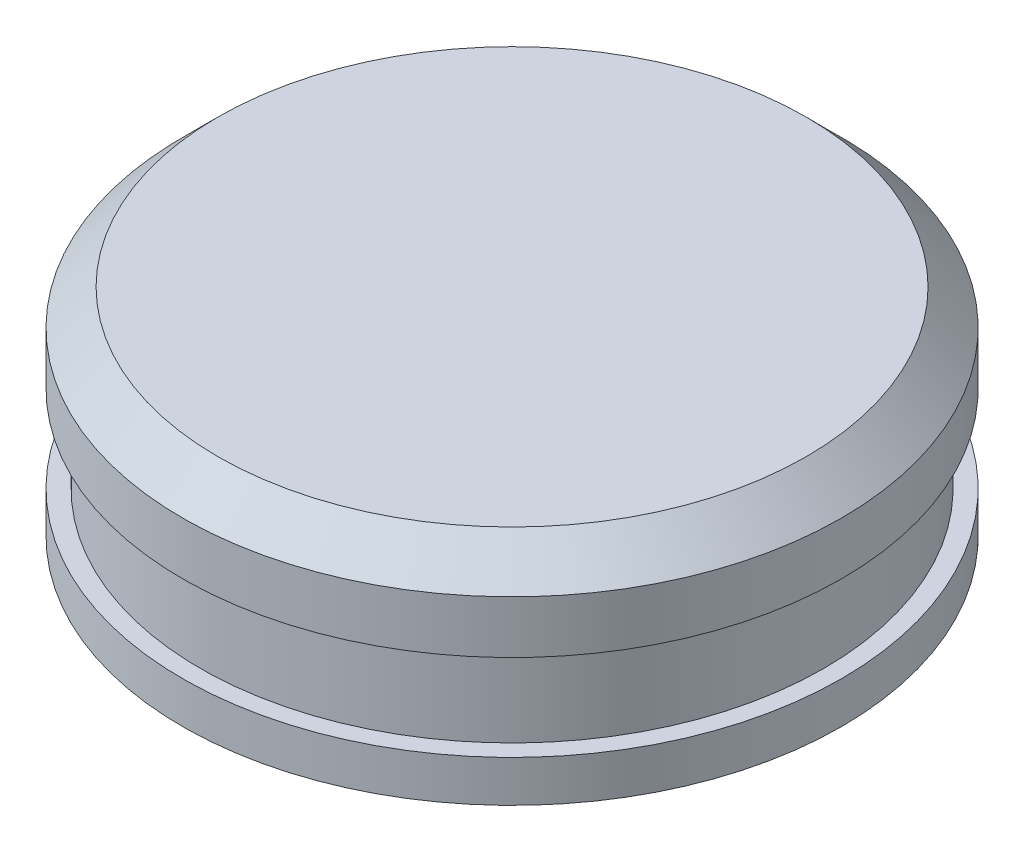
SolidWorks part; units mm, degrees
material "PET"
ref_plane "Front Plane" through (0, 0, 0) normal (0, 0, 1) x (1, 0, 0)
ref_plane "Top Plane" through (0, 0, 0) normal (0, 1, 0) x (1, 0, 0)
ref_plane "Right Plane" through (0, 0, 0) normal (1, 0, 0) x (0, 0, -1)
sketch "Sketch1" plane through (0, 0, 0) normal (0, 0, 1) x (1, 0, 0)
  line L0 (0, 0) -> (0, 15) construction
  line L1 (0, 15) -> (44.439, 15)
  line L2 (44.439, 15) -> (44.439, 0)
  line L3 (44.439, 0) -> (53, 0)
  line L4 (53, 0) -> (53, 6.681)
  line L5 (53, 6.681) -> (50.1531, 6.681)
  line L6 (50.1531, 6.681) -> (50.1531, 20.5903)
  line L7 (50.1531, 20.5903) -> (53, 20.5903)
  line L8 (53, 20.5903) -> (53, 29.0497)
  line L9 (53, 29.0497) -> (47.3062, 34.7435)
  line L10 (47.3062, 34.7435) -> (0, 34.7435)
  line L11 (0, 34.7435) -> (0, 15)
  dimension "D1" = 106
  dimension "D2" = 88.8779
revolve "body" add sketch "Sketch1" angle 360 about L0
equation "\"paper_size\" = 600mm"
equation "\"cb_roll_d_outer\" = 80mm"
equation "\"cb_roll_d_inner\" = 78mm"
equation "\"helper_d\" = 86mm"
equation "\"outer_d\" = 106mm"
equation "\"spring_l_max\" = 25mm"
equation "\"spring_l_min\" = 10mm"
equation "\"D1@Sketch1\"=\"outer_d\""
